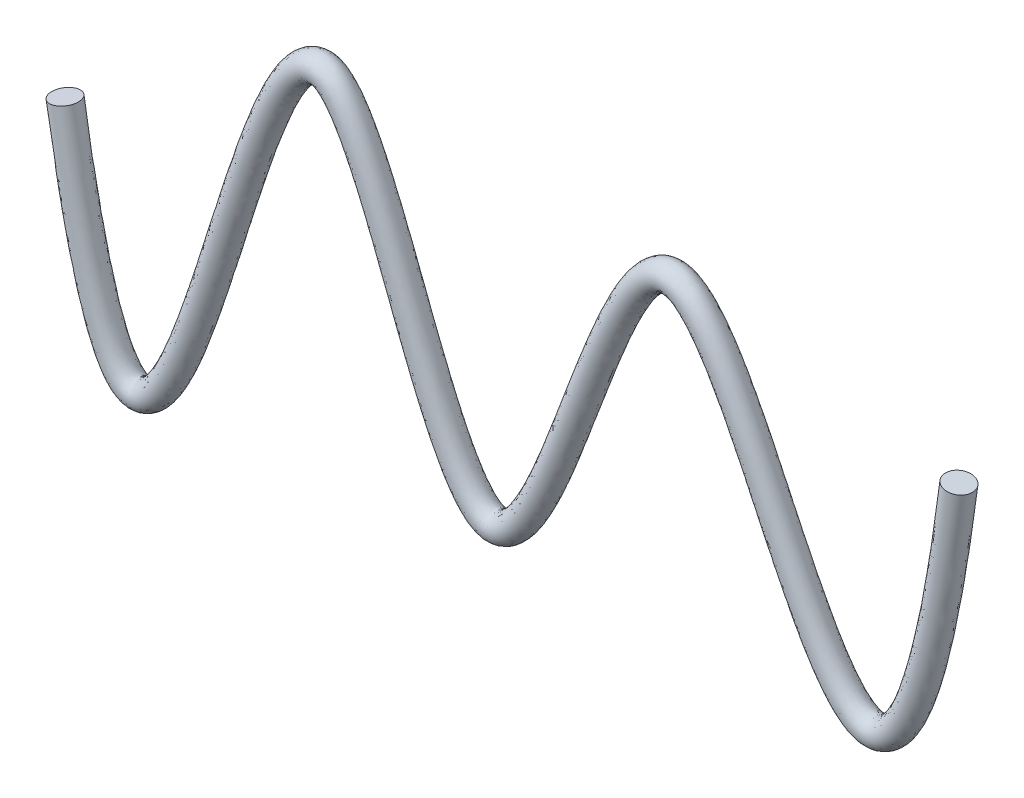
SolidWorks part; units mm, degrees
ref_plane "Front Plane" through (0, 0, 0) normal (0, 0, 1) x (1, 0, 0)
ref_plane "Top Plane" through (0, 0, 0) normal (0, 1, 0) x (1, 0, 0)
ref_plane "Right Plane" through (0, 0, 0) normal (1, 0, 0) x (0, 0, -1)
sketch "Sketch1" plane through (0, 0, 0) normal (0, 0, 1) x (1, 0, 0)
  spline S0 degree 3 poles (-64.3523, 5.5449) (-53.8112, -59.1798) (-40.9551, 75.5813) (-16.1162, -43.1377) (5.1498, 70.6569) (25.9539, -49.4019) (34.7732, 18.0522) knots 0 0 0 0 0.328428 0.515707 0.70019 1 1 1 1
ref_plane "Plane1" through (34.7732, 18.0522, 0) normal (0.1296, 0.9916, 0) x (0.9916, -0.1296, 0)
sketch "Sketch2" plane through (34.7732, 18.0522, 0) normal (0.1296, 0.9916, 0) x (0.9916, -0.1296, 0)
  line L0 (-96.6675, 0) -> (0, 0) construction
  circle A0 centre (0, 0) radius 1.5
  dimension "D1" = 3
sweep "Sweep1" add profiles "Sketch2" path "Sketch1"
